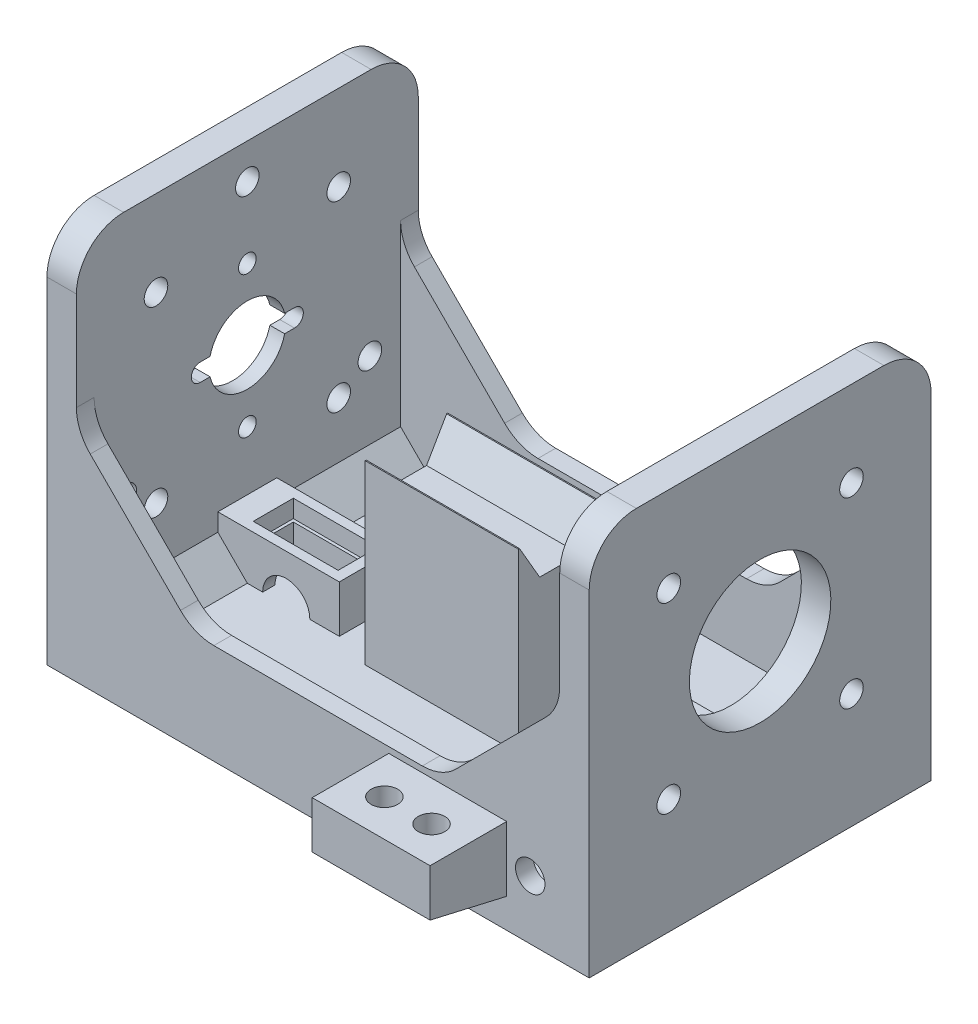
SolidWorks part; units mm, degrees
ref_plane "Plano frontal" through (0, 0, 0) normal (0, 0, 1) x (1, 0, 0)
ref_plane "Plano superior" through (0, 0, 0) normal (0, 1, 0) x (1, 0, 0)
ref_plane "Plano direito" through (0, 0, 0) normal (1, 0, 0) x (0, 0, -1)
sketch "Esboço1" plane through (0, 0, 0) normal (0, 0, 1) x (1, 0, 0)
  line L0 (0, 0) -> (-41, 0)
  line L1 (-41, 0) -> (-41, 60)
  line L2 (-41, 60) -> (-46, 60)
  line L3 (-46, 60) -> (-46, -5)
  line L4 (-46, -5) -> (46, -5)
  line L5 (46, -5) -> (46, 60)
  line L6 (46, 60) -> (41, 60)
  line L7 (41, 60) -> (41, 0)
  line L8 (41, 0) -> (0, 0)
  dimension "D1" = 41
  dimension "D2" = 41
  dimension "D3" = 60
  dimension "D4" = 5
  dimension "D5" = 5
  dimension "D6" = 5
  dimension "D7" = 60
extrude "Ressalto-extrusão1" add sketch "Esboço1" along normal mid plane 58
sketch "Esboço2" plane through (-46, 0, 0) normal (-1, 0, 0) x (0, 0, 1)
  line L0 (29, -5) -> (-29, -5) construction
  circle A0 centre (0, 30) radius 6.5
  dimension "D1" = 13
  dimension "D2" = 35
extrude "Corte-extrusão1" cut sketch "Esboço2" against normal up to next
sketch "Esboço3" plane through (-46, 0, 0) normal (-1, 0, 0) x (0, 0, 1)
  circle A0 centre (0, 30) radius 18
  dimension "D1" = 36
extrude "Corte-extrusão2" cut sketch "Esboço3" against normal blind 2.5
sketch "Esboço5" plane through (-46, 0, 0) normal (-1, 0, 0) x (0, 0, 1)
  line L0 (0, 60) -> (0, -5) construction
  line L1 (29, 60) -> (-29, 60) construction
  line L2 (29, -5) -> (-29, -5) construction
  line L3 (-18, 30) -> (18, 30) construction
  line L4 (-8, 31.5) -> (8, 31.5)
  line L5 (-8, 28.5) -> (8, 28.5)
  arc A0 (-8, 31.5) -> (-8, 28.5) centre (-8, 30) ccw
  arc A1 (8, 31.5) -> (8, 28.5) centre (8, 30) cw
  circle A2 centre (-15.5, 45.5) radius 2
  circle A3 centre (0, 30) radius 18 construction
  circle A7 centre (0, 42) radius 1.5
  circle A8 centre (0, 30) radius 6.5 construction
  circle A9 centre (0, 30) radius 18 construction
  circle A10 centre (0, 18) radius 1.5
  circle A11 centre (0, 54) radius 2
  circle A14 centre (15.5, 45.5) radius 2
  circle A15 centre (15.5, 14.5) radius 2
  circle A16 centre (-15.5, 14.5) radius 2
  circle A17 centre (20.7846, 18) radius 2
  circle A18 centre (-20.7846, 18) radius 2
  point P23 (-2.3598, 32.3598)
  point P43 (1.3625, 32.3598)
  point P44 (0, 30)
  point P45 (0, 30)
  dimension "D1" = 8
  dimension "D2" = 3
  dimension "D3" = 4
  dimension "D4" = 15.5
  dimension "D5" = 15.5
  dimension "D7" = 12
  dimension "D8" = 3
  dimension "D9" = 4
  dimension "D10" = 24
  dimension "D12" = 0
  dimension "D6" = 4
  dimension "D11" = 3
extrude "Corte-extrusão3" cut sketch "Esboço5" against normal up to next (5 mm away)
sketch "Esboço7" plane through (41, 0, 0) normal (-1, 0, 0) x (0, 0, 1)
  circle A0 centre (0, 30) radius 12
  circle A1 centre (-15.5, 45.5) radius 2
  circle A6 centre (15.5, 45.5) radius 2
  circle A7 centre (15.5, 14.5) radius 2
  circle A8 centre (-15.5, 14.5) radius 2
  point P14 (-2.3598, 32.3598)
  point P15 (0, 30)
  dimension "D1" = 24
  dimension "D2" = 15.5
  dimension "D3" = 15.5
  dimension "D4" = 4
  dimension "D5" = 4
extrude "Corte-extrusão4" cut sketch "Esboço7" against normal through all
sketch "Esboço11" plane through (0, 0, 0) normal (0, 1, 0) x (1, 0, 0)
  line L0 (-41, -29) -> (-41, 29) construction
  line L1 (-38.4, 5) -> (-20.4, 5)
  line L2 (-38.4, 5) -> (-38.4, -5)
  line L3 (-38.4, -5) -> (-20.4, -5)
  line L4 (-20.4, 5) -> (-20.4, -5)
  dimension "D1" = 5
  dimension "D2" = 5
  dimension "D3" = 18
  dimension "D4" = 2.6
extrude "Ressalto-extrusão3" add sketch "Esboço11" along normal blind 8
sketch "Esboço12" plane through (0, 8, 0) normal (0, 1, 0) x (1, 0, 0)
  line L0 (-38.4, 5) -> (-38.4, -5) construction
  line L1 (-36.6, -3.4) -> (-22.2, -3.4)
  line L2 (-36.6, -3.4) -> (-36.6, 3.4)
  line L3 (-36.6, 3.4) -> (-22.2, 3.4)
  line L4 (-22.2, -3.4) -> (-22.2, 3.4)
  line L5 (-36.6, -3.4) -> (-22.2, 3.4) construction
  line L6 (-36.6, 3.4) -> (-22.2, -3.4) construction
  line L12 (-20.4, 5) -> (-38.4, 5) construction
  point P0 (-29.4, 0)
  point P7 (-38.4, 0)
  point P10 (-25.6011, -0.044)
  point P11 (-29.4, 5)
  dimension "D1" = 0
  dimension "D2" = 14.4
  dimension "D3" = 6.8
  dimension "D4" = 0
extrude "Corte-extrusão6" cut sketch "Esboço12" against normal blind 3
sketch "Esboço13" plane through (0, 5, 0) normal (0, 1, 0) x (1, 0, 0)
  line L0 (-22.2, 3.4) -> (-36.6, 3.4) construction
  line L1 (-36.1, -2.9) -> (-22.7, -2.9)
  line L2 (-36.1, -2.9) -> (-36.1, 2.9)
  line L3 (-36.1, 2.9) -> (-22.7, 2.9)
  line L4 (-22.7, -2.9) -> (-22.7, 2.9)
  line L5 (-36.1, -2.9) -> (-22.7, 2.9) construction
  line L6 (-36.1, 2.9) -> (-22.7, -2.9) construction
  line L7 (-22.2, -3.4) -> (-22.2, 3.4) construction
  line L8 (-36.6, -3.4) -> (-22.2, -3.4) construction
  point P0 (-29.4, 0)
  point P7 (-29.4, 3.4)
  dimension "D1" = 0
  dimension "D2" = 0.5
  dimension "D3" = 0.5
  dimension "D4" = 0.5
extrude "Corte-extrusão7" cut sketch "Esboço13" against normal up to surface (5 mm away) up to face at (0, 0, 0)
sketch "Esboço14" plane through (0, 0, 5) normal (0, 0, 1) x (1, 0, 0)
  line L0 (-38.4, 0) -> (-20.4, 0) construction
  line L1 (-33.4, 0) -> (-25.4, 0)
  arc A0 (-25.4, 0) -> (-33.4, 0) centre (-29.4, 0) ccw
  dimension "D1" = 8
extrude "Corte-extrusão8" cut sketch "Esboço14" against normal up to next
sketch "Esboço16" plane through (0, 0, 29) normal (0, 0, 1) x (1, 0, 0)
  line L0 (-41, 32) -> (-21, 12)
  line L1 (-41, 0) -> (-41, 60) construction
  line L2 (-21, 12) -> (21, 12)
  line L3 (21, 12) -> (41, 32)
  line L4 (41, 60) -> (41, 0) construction
  line L5 (41, 32) -> (41, 0)
  line L6 (41, 0) -> (-41, 0)
  line L7 (-41, 0) -> (-41, 32)
  dimension "D1" = 32
  dimension "D2" = 32
  dimension "D3" = 12
  dimension "D4" = 20
  dimension "D5" = 20
extrude "Ressalto-extrusão4" add sketch "Esboço16" against normal blind 3
mirror "Espelhar1" about plane through (0, 0, 0) normal (0, 0, 1) of "Ressalto-extrusão4"
sketch "Esboço17" plane through (0, 8, 0) normal (0, 1, 0) x (1, 0, 0)
  line L0 (-41, -26) -> (-41, 26) construction
  line L1 (-38.4, 5) -> (-41, 5)
  line L2 (-38.4, 5) -> (-38.4, -5)
  line L3 (-38.4, -5) -> (-41, -5)
  line L4 (-41, 5) -> (-41, -5)
extrude "Ressalto-extrusão5" add sketch "Esboço17" against normal up to surface (8 mm away) up to face at (0, 0, 0)
chamfer "Chanfro1" distance 5 angle 45 3 edges at (41, 0, 0) (-41, 0, -15.5) (-41, 0, 15.5)
fillet "Filete1" radius 8 12 edges at (21, 12, 27.5) (41, 32, 27.5) (41, 32, -27.5) (21, 12, -27.5) (-41, 32, 27.5) (-21, 12, 27.5) (-21, 12, -27.5) (-41, 32, -27.5) (43.5, 60, -29) (43.5, 60, 29) (-43.5, 60, 29) (-43.5, 60, -29)
sketch "Esboço18" plane through (0, 0, 29) normal (0, 0, 1) x (1, 0, 0)
  line L0 (46, -5) -> (46, 52) construction
  line L1 (12, 3) -> (32, 3)
  line L2 (12, 3) -> (12, 11)
  line L3 (12, 11) -> (32, 11)
  line L4 (32, 3) -> (32, 11)
  line L5 (-46, -5) -> (46, -5) construction
  dimension "D1" = 8
  dimension "D2" = 20
  dimension "D3" = 14
  dimension "D4" = 8
extrude "Ressalto-extrusão6" add sketch "Esboço18" along normal blind 13
sketch "Esboço19" plane through (0, 11, 0) normal (0, 1, 0) x (1, 0, 0)
  line L0 (32, -42) -> (12, -42) construction
  circle A0 centre (18, -35.75) radius 2.25
  circle A1 centre (26, -35.75) radius 2.25
  point P6 (22, -42)
  dimension "D1" = 4.5
  dimension "D2" = 4.5
  dimension "D3" = 8
  dimension "D4" = 4
  dimension "D5" = 6.25
extrude "Corte-extrusão9" cut sketch "Esboço19" against normal through all
chamfer "Chanfro2" distance 3 distance2 13 1 edges at (22, 3, 29) first distance on face at (0, 27.074, 29)
sketch "Esboço20" plane through (0, 11, 0) normal (0, 1, 0) x (1, 0, 0)
  line L0 (18, -31.5) -> (26, -31.5)
  line L1 (18, -40) -> (26, -40)
  arc A0 (18, -31.5) -> (18, -40) centre (18, -35.75) ccw
  arc A1 (26, -40) -> (26, -31.5) centre (26, -35.75) ccw
  dimension "D1" = 8.5
  dimension "D2" = 8.5
extrude "Corte-extrusão10" cut sketch "Esboço20" against normal through all from offset 6 offset against normal yes
sketch "Esboço21" plane through (0, 0, 0) normal (0, 1, 0) x (1, 0, 0)
  line L1 (-14, 7) -> (12, 7)
  line L2 (-14, 7) -> (-14, -7)
  line L3 (-14, -7) -> (12, -7)
  line L4 (12, 7) -> (12, -7)
  dimension "D1" = 7
  dimension "D2" = 7
  dimension "D3" = 14
  dimension "D4" = 12
extrude "Ressalto-extrusão7" add sketch "Esboço21" along normal blind 30
sketch "Esboço22" plane through (12, 0, 0) normal (1, 0, 0) x (0, 0, -1)
  line L0 (-7, 30) -> (7, 30) construction
  line L1 (6.8127, 30) -> (3.4064, 35.9)
  line L2 (3.4064, 35.9) -> (-3.4064, 35.9)
  line L3 (-3.4064, 35.9) -> (-6.8127, 30)
  line L4 (-6.8127, 30) -> (-3.4064, 24.1)
  line L5 (-3.4064, 24.1) -> (3.4064, 24.1)
  line L6 (3.4064, 24.1) -> (6.8127, 30)
  circle A0 centre (0, 30) radius 5.9 construction
  dimension "D1" = 11.8
extrude "Corte-extrusão11" cut sketch "Esboço22" against normal up to surface (26 mm away) up to face at (-14, 15, 0)
sketch "Esboço24" plane through (0, 0, 0) normal (0, 1, 0) x (1, 0, 0)
  line L0 (17.2823, 14.5) -> (32.4823, 14.5)
  line L1 (17.2823, 10.5) -> (32.4823, 10.5)
  line L2 (-36, 26) -> (36, 26) construction
  line L4 (16.2823, -6.5) -> (33.4823, -6.5)
  line L5 (16.2823, -6.5) -> (16.2823, -9.5)
  line L6 (16.2823, -9.5) -> (33.4823, -9.5)
  line L7 (33.4823, -6.5) -> (33.4823, -9.5)
  circle A0 centre (17.2823, 12.5) radius 1
  circle A1 centre (32.4823, 12.5) radius 1
  arc A2 (17.2823, 14.5) -> (17.2823, 10.5) centre (17.2823, 12.5) ccw
  arc A3 (32.4823, 10.5) -> (32.4823, 14.5) centre (32.4823, 12.5) ccw
  dimension "D1" = 15.2
  dimension "D2" = 2
  dimension "D3" = 2
  dimension "D4" = 4
  dimension "D5" = 4
  dimension "D6" = 11.5
  dimension "D7" = 3
  dimension "D8" = 17
  dimension "D9" = 1
  dimension "D10" = 1
extrude "Ressalto-extrusão8" add sketch "Esboço24" along normal blind 3
sketch "Esboço25" plane through (0, 3, 0) normal (0, 1, 0) x (1, 0, 0)
  line L0 (32.4823, 14.5) -> (17.2823, 14.5) construction
  line L1 (19.2823, 14.5) -> (30.4823, 14.5)
  line L2 (19.2823, 14.5) -> (19.2823, 10.5)
  line L3 (19.2823, 10.5) -> (30.4823, 10.5)
  line L4 (30.4823, 14.5) -> (30.4823, 10.5)
  line L5 (17.2823, 10.5) -> (32.4823, 10.5) construction
  circle A0 centre (17.2823, 12.5) radius 1 construction
  circle A1 centre (32.4823, 12.5) radius 1 construction
  dimension "D1" = 2
  dimension "D2" = 2
extrude "Corte-extrusão12" cut sketch "Esboço25" against normal blind 2
sketch "Esboço26" plane through (0, 0, 29) normal (0, 0, 1) x (1, 0, 0)
  line L0 (-46, -5) -> (46, -5) construction
  line L1 (46, -5) -> (46, 52) construction
  circle A0 centre (36, 5) radius 2.5
  dimension "D1" = 5
  dimension "D2" = 10
  dimension "D3" = 10
extrude "Corte-extrusão13" cut sketch "Esboço26" against normal through all
sketch "Esboço27" plane through (0, 0, 0) normal (0, 1, 0) x (1, 0, 0)
  line L0 (-41, -21) -> (-41, 21) construction
  line L1 (-16, 20.5) -> (8, 20.5)
  line L2 (-16, 20.5) -> (-16, 12.5)
  line L3 (-16, 12.5) -> (8, 12.5)
  line L4 (8, 20.5) -> (8, 12.5)
  line L5 (17.6863, 26) -> (-17.6863, 26) construction
  dimension "D1" = 8
  dimension "D2" = 24
  dimension "D3" = 25
  dimension "D4" = 5.5
extrude "Ressalto-extrusão9" add sketch "Esboço27" along normal blind 6
sketch "Esboço28" plane through (0, 6, 0) normal (0, 1, 0) x (1, 0, 0)
  line L0 (-16, 12.5) -> (8, 12.5) construction
  line L1 (-16, 20.5) -> (-14.5, 20.5)
  line L2 (-16, 20.5) -> (-16, 12.5)
  line L3 (-16, 12.5) -> (-14.5, 12.5)
  line L4 (-14.5, 20.5) -> (-14.5, 12.5)
  line L6 (8, 20.5) -> (6.5, 20.5)
  line L7 (8, 20.5) -> (8, 12.5)
  line L8 (8, 12.5) -> (6.5, 12.5)
  line L9 (6.5, 20.5) -> (6.5, 12.5)
  dimension "D1" = 1.5
  dimension "D2" = 1.5
extrude "Ressalto-extrusão10" add sketch "Esboço28" along normal blind 2
